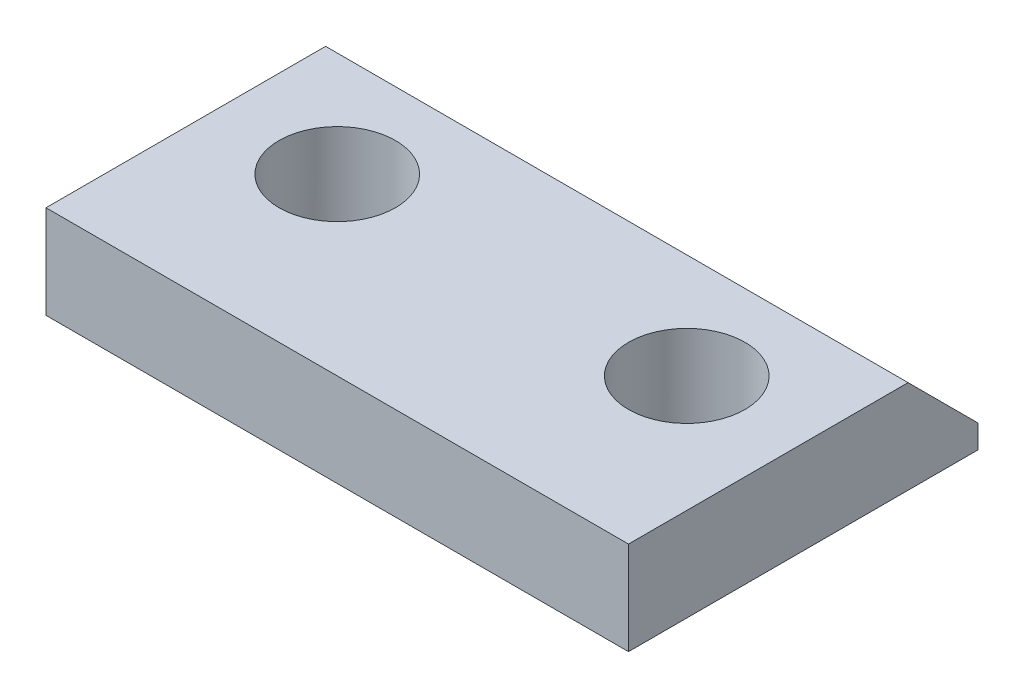
SolidWorks part; units mm, degrees
ref_plane "Front Plane" through (0, 0, 0) normal (0, 0, 1) x (1, 0, 0)
ref_plane "Top Plane" through (0, 0, 0) normal (0, 1, 0) x (1, 0, 0)
ref_plane "Right Plane" through (0, 0, 0) normal (1, 0, 0) x (0, 0, -1)
sketch "Sketch1" plane through (0, 0, 0) normal (0, 1, 0) x (1, 0, 0)
  line L1 (-12.5, -7.5) -> (12.5, -7.5)
  line L2 (-12.5, -7.5) -> (-12.5, 7.5)
  line L3 (-12.5, 7.5) -> (12.5, 7.5)
  line L4 (12.5, -7.5) -> (12.5, 7.5)
  line L5 (-12.5, -7.5) -> (12.5, 7.5) construction
  line L6 (-12.5, 7.5) -> (12.5, -7.5) construction
  point P0 (0, 0)
  dimension "D1" = 25
  dimension "D2" = 15
extrude "Boss-Extrude1" add sketch "Sketch1" along normal blind 3
hole_wizard "Ø1.0mm Dowel Hole1" positions "Sketch2" profile "Sketch4" hole size "Ø1.0" standard "ANSI Metric" end condition through all
sketch "Sketch2" plane through (0, 3, 0) normal (0, 1, 0) x (1, 0, 0)
  line L0 (-7.5, 0) -> (7.5, 0)
  point P0 (-7.5, 0)
  point P1 (7.5, 0)
  point P3 (0, 0)
  dimension "D1" = 15
sketch "Sketch4" plane through (-7.5, 3, 0) normal (1, 0, 0) x (0, 0, 1)
  line L0 (0, 0) -> (0, 3)
  line L1 (0, 3) -> (2.5, 3)
  line L2 (2.5, 3) -> (2.5, 0)
  line L5 (2.5, 0) -> (0, 0)
  line L11 (0, -6.35) -> (0, 107.95) construction
  dimension "Thru Hole Dia." = 5
  dimension "Thru Hole Depth" = 3
chamfer "Chamfer1" distance 3 angle 45 1 edges at (0, 3, -7.5)
sketch "Sketch5" plane through (0, 0, 0) normal (0, -1, 0) x (1, 0, 0)
  line L4 (12.5, -7.5) -> (12.5, 7.5)
  line L5 (12.5, 7.5) -> (-12.5, 7.5)
  line L6 (-12.5, 7.5) -> (-12.5, -7.5)
  line L7 (-12.5, -7.5) -> (12.5, -7.5)
  line L8 (12.5, -7.5) -> (12.5, 7.5)
  line L9 (12.5, 7.5) -> (-12.5, 7.5)
  line L10 (-12.5, 7.5) -> (-12.5, -7.5)
  line L11 (-12.5, -7.5) -> (12.5, -7.5)
  circle A0 centre (-7.5, 0) radius 2.5 construction
  circle A1 centre (7.5, 0) radius 2.5 construction
  circle A2 centre (-7.5, 0) radius 2.5
  circle A3 centre (7.5, 0) radius 2.5
  dimension "D1" = 0
extrude "Boss-Extrude2" add sketch "Sketch5" along normal blind 1
